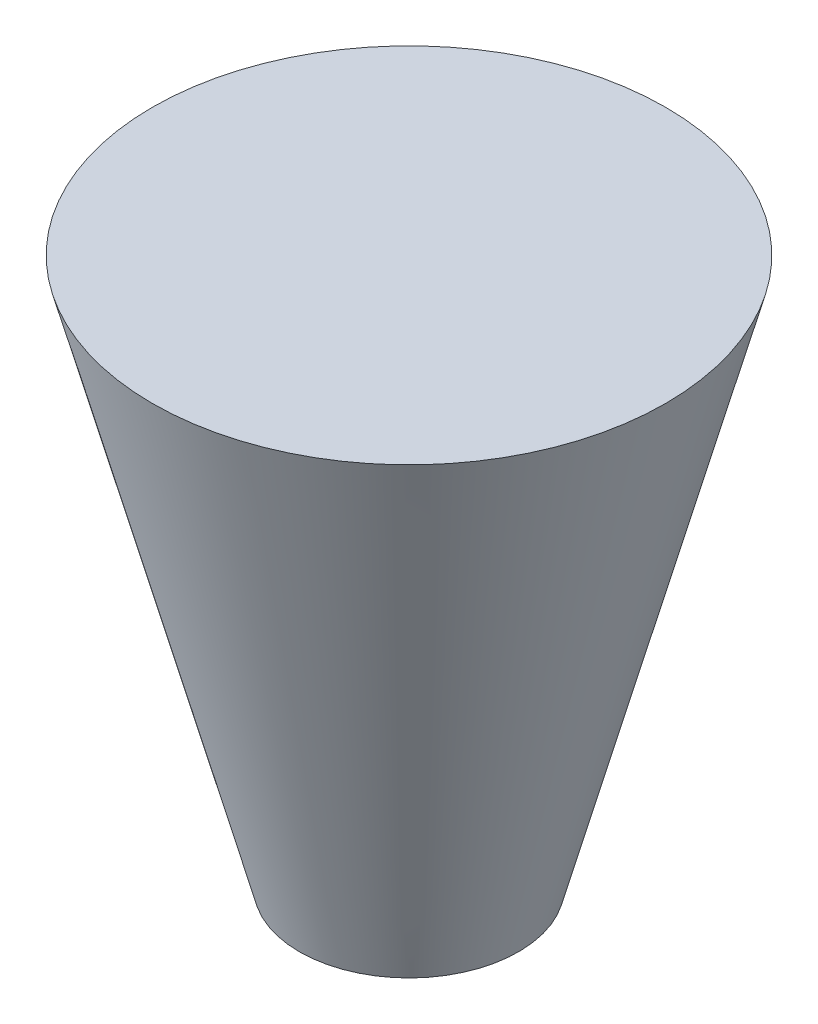
SolidWorks part; units mm, degrees
ref_plane "Front Plane" through (0, 0, 0) normal (0, 0, 1) x (1, 0, 0)
ref_plane "Top Plane" through (0, 0, 0) normal (0, 1, 0) x (1, 0, 0)
ref_plane "Right Plane" through (0, 0, 0) normal (1, 0, 0) x (0, 0, -1)
sketch "Sketch1" plane through (0, 0, 0) normal (0, 1, 0) x (1, 0, 0)
  circle A0 centre (0, 0) radius 10
  dimension "D1" = 20
extrude "Boss-Extrude1" add sketch "Sketch1" along normal blind 50 draft 15 draft outward yes
